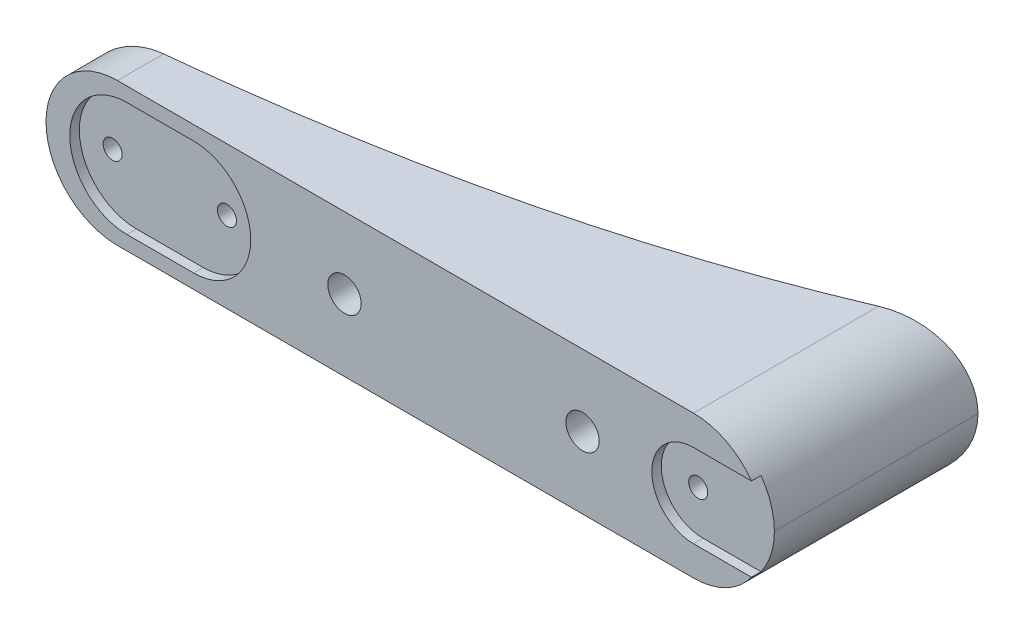
SolidWorks part; units mm, degrees
note: The reader was unsure of these and kept them because the rebuilt part matched: shared geometry of "Sketch2<6>", "Sketch2<7>".
material "Delrin 2700 NC010, Low Viscosity Acetal Copolymer (SS)"
ref_plane "Front Plane" through (0, 0, 0) normal (0, 0, 1) x (1, 0, 0)
ref_plane "Top Plane" through (0, 0, 0) normal (0, 1, 0) x (1, 0, 0)
ref_plane "Right Plane" through (0, 0, 0) normal (1, 0, 0) x (0, 0, -1)
sketch "Sketch1" plane through (0, 0, 0) normal (0, 1, 0) x (1, 0, 0)
  line L0 (-75.5, 0) -> (75.5, 0)
  line L1 (75.5, 0) -> (75.5, 7)
  line L2 (75.5, 7) -> (49.7, 7)
  line L3 (49.7, 7) -> (49.7, 30)
  line L4 (49.7, 30) -> (-25.3, 30)
  line L5 (-25.3, 30) -> (-25.3, 7)
  line L6 (-25.3, 7) -> (-75.5, 7)
  line L7 (-75.5, 7) -> (-75.5, 0)
  line L8 (0, 30) -> (0, 0) construction
  line L9 (12.2, 30) -> (12.2, 0) construction
  line L10 (-25.3, 7) -> (49.7, 7)
  dimension "D1" = 151
  dimension "D2" = 7
  dimension "D3" = 30
  dimension "D4" = 75
  dimension "D5" = 87.7
extrude "Boss-Extrude1" add sketch "Sketch1" along normal blind 30 contours L10 L6 L7 L0 L1 L2
sketch "Sketch10" plane through (0, 0, -7) normal (0, 0, -1) x (-1, 0, 0)
  line L4 (-75.5, 0) -> (75.5, 0)
  line L5 (75.5, 0) -> (75.5, 30)
  line L6 (75.5, 30) -> (-75.5, 30)
  line L7 (-75.5, 30) -> (-75.5, 0)
  line L8 (-75.5, 0) -> (75.5, 0)
  line L9 (75.5, 0) -> (75.5, 30)
  line L10 (75.5, 30) -> (-75.5, 30)
  line L11 (-75.5, 30) -> (-75.5, 0)
  dimension "D1" = 0
extrude "Boss-Extrude2" add sketch "Sketch10" along normal blind 40
ref_plane "Plane1" through (0, 15, 0) normal (0, 1, 0) x (1, 0, 0)
sketch "Sketch13" plane through (0, 15, 0) normal (0, 1, 0) x (1, 0, 0)
  line L0 (213.0573, 170) -> (-103.5, 170) construction
  line L1 (213.0573, 147.5) -> (-103.5, 147.5)
  line L2 (-103.5, 147.5) -> (-103.5, 5.8074)
  spline S2 degree 3 poles (-103.5, 5.8074) (-21.1701, 9.7777) (50.1722, 25.996) (136.8446, 80.3457) (186.5493, 122.8944) (213.0573, 147.5) knots 0 0 0 0 0.647236 0.769472 1 1 1 1
  spline S3 degree 3 poles (213.0573, 192.5) (186.5493, 217.1056) (136.8446, 259.6543) (50.1722, 314.004) (-21.1701, 330.2223) (-103.5, 334.1926) knots 0 0 0 0 0.230528 0.352764 1 1 1 1 construction
revolve "Cut-Revolve1" cut sketch "Sketch13" angle 360 about L0
sketch "Sketch2" plane through (0, 0, 0) normal (0, 0, 1) x (1, 0, 0)
  line L0 (60.5, 23.75) -> (75.5, 23.75)
  line L1 (-75.5, 15) -> (75.5, 15) construction
  line L2 (-51.5, 27) -> (-51.5, 3) construction
  line L3 (-75.5, 30) -> (-75.5, 0) construction
  line L4 (60.5, 6.25) -> (75.5, 6.25)
  line L5 (-58.5, 15) -> (-44.5, 15) construction
  line L6 (-58.5, 27) -> (-44.5, 27)
  line L7 (-58.5, 3) -> (-44.5, 3)
  line L8 (75.5, 30) -> (75.5, 0) construction
  line L9 (75.5, 6.25) -> (75.5, 23.75)
  circle A0 centre (59.5, 15) radius 2
  arc A1 (-58.5, 27) -> (-58.5, 3) centre (-58.5, 15) ccw
  arc A2 (-44.5, 3) -> (-44.5, 27) centre (-44.5, 15) ccw
  circle A3 centre (-63.5, 15) radius 2
  circle A4 centre (-39.5, 15) radius 2
  arc A5 (60.5, 23.75) -> (60.5, 6.25) centre (60.5, 15) ccw
  point P14 (-70.5, 15)
  point P18 (-51.5, 15)
  dimension "D4" = 4
  dimension "D7" = 12
  dimension "D3" = 17.5
  dimension "D2" = 1
  dimension "D6" = 14
  dimension "D8" = 24
  dimension "D9" = 99
  dimension "D10" = 5
extrude "Cut-Extrude1" cut sketch "Sketch2" against normal through all contours A4 | A0 | A3
extrude "Cut-Extrude2" cut sketch "Sketch2<6>" against normal blind 2 contours L7 A2 L6 A1 A4 A3
sketch "Sketch2<6>" plane through (0, 0, 0) normal (0, 0, 1) x (1, 0, 0) same geometry as "Sketch2"
extrude "Cut-Extrude3" cut sketch "Sketch2<7>" against normal blind 2 contours A5 A0
sketch "Sketch2<7>" plane through (0, 0, 0) normal (0, 0, 1) x (1, 0, 0) same geometry as "Sketch2"
sketch "Sketch6" plane through (0, 0, 0) normal (0, 0, -1) x (-1, 0, 0)
  line L1 (75.5, 15) -> (-75.5, 15) construction
  line L3 (75.5, 0) -> (75.5, 30) construction
  line L4 (-75.5, 30) -> (-75.5, 0) construction
  circle A0 centre (12.8, 15) radius 2.75
  circle A1 centre (-37.2, 15) radius 2.75
  dimension "D2" = 5.5
  dimension "D1" = 50
  dimension "D3" = 12.8
hole_wizard "Ø7.0 (7) Diameter Hole1" positions "Sketch8" profile "Sketch7" hole size "Ø7.0" standard "ANSI Metric" end condition up to next
sketch "Sketch8" plane through (0, 0, 0) normal (0, 0, -1) x (-1, 0, 0)
  point P0 (-37.2, 15)
  point P3 (12.8, 15)
sketch "Sketch7" plane through (37.2, 15, 0) normal (1, 0, 0) x (0, -1, 0)
  line L0 (0, 0) -> (0, 29.2)
  line L1 (0, 29.2) -> (3.5, 29.2)
  line L2 (3.5, 29.2) -> (3.5, 0)
  line L5 (3.5, 0) -> (0, 0)
  line L11 (0, -6.35) -> (0, 107.95) construction
  dimension "Thru Hole Dia." = 7
  dimension "Thru Hole Depth" = 29.2
sketch "Sketch9" plane through (0, 0, 0) normal (0, 0, -1) x (-1, 0, 0)
  circle A0 centre (-59.5, 15) radius 3.5
  circle A1 centre (39.5, 15) radius 3.5
  circle A2 centre (63.5, 15) radius 3.5
  dimension "D1" = 7
extrude "Cut-Extrude5" cut sketch "Sketch9" along normal through all from offset 5
fillet "Fillet1" radius 15 4 edges at (75.5, 30, -22.8345) (-75.5, 0, -4.1525) (75.5, 0, -22.8345) (-75.5, 30, -4.1525)
